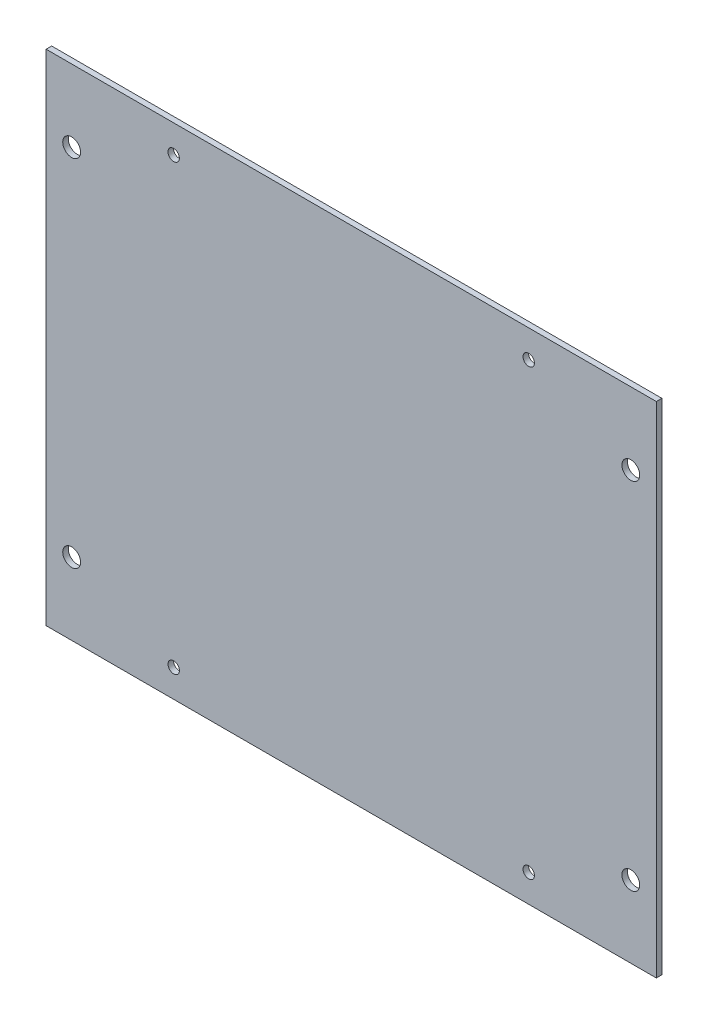
SolidWorks part; units mm, degrees
material "Perspex (TM) GS Acrylic Cast Sheet"
ref_plane "Front Plane" through (0, 0, 0) normal (0, 0, 1) x (1, 0, 0)
ref_plane "Top Plane" through (0, 0, 0) normal (0, 1, 0) x (1, 0, 0)
ref_plane "Right Plane" through (0, 0, 0) normal (1, 0, 0) x (0, 0, -1)
sketch "Sketch1" plane through (0, 0, 0) normal (0, 0, 1) x (1, 0, 0)
  line L1 (-457.2, -304.8) -> (457.2, -304.8)
  line L2 (-457.2, -304.8) -> (-457.2, 304.8)
  line L3 (-457.2, 304.8) -> (457.2, 304.8)
  line L4 (457.2, -304.8) -> (457.2, 304.8)
  line L5 (0, 304.8) -> (0, -304.8) construction
  line L6 (-457.2, 0) -> (457.2, 0) construction
  point P0 (0, 0)
  point P4 (-320.04, 0)
  point P5 (320.04, 0)
  point P6 (0, 213.36)
  point P7 (0, -213.36)
  dimension "Length" = 914.4
  dimension "Width" = 609.6
  dimension "Break" = 137.16
  dimension "D2" = 137.16
  dimension "D1" = 91.44
  dimension "D3" = 91.44
sketch "Sketch2" plane through (0, 0, 0) normal (1, 0, 0) x (0, 0, -1)
  line L0 (-0.7938, -304.8) -> (0.7938, -304.8)
  dimension "Thickness" = 1.5875
sketch "Sketch3" plane through (0, 0, 0) normal (0, 0, 1) x (1, 0, 0)
  line L0 (-457.2, -304.8) -> (-457.2, 304.8) construction
  line L1 (-457.2, -304.8) -> (457.2, -304.8) construction
  line L2 (457.2, -304.8) -> (457.2, 304.8) construction
  line L3 (-457.2, 304.8) -> (457.2, 304.8) construction
  line L4 (-457.2, -304.8) -> (-457.2, 304.8)
  line L5 (-457.2, -304.8) -> (457.2, -304.8)
  line L6 (457.2, -304.8) -> (457.2, 304.8)
  line L7 (-457.2, 304.8) -> (457.2, 304.8)
extrude "Boss-Extrude1" add sketch "Sketch3" along normal mid plane 1.5875
sketch "Sketch4" plane through (0, 0, -0.7937) normal (0, 0, -1) x (-1, 0, 0)
  line L0 (393.5597, -82.9526) -> (218.9347, -82.9526)
  line L1 (218.9347, -82.9526) -> (218.9347, 59.9224)
  line L2 (218.9347, 59.9224) -> (393.5597, 59.9224)
  line L3 (393.5597, 59.9224) -> (393.5597, -82.9526)
extrude "Cut-Extrude1" cut sketch "Sketch4" against normal blind 2.54 flip side to cut
hole_wizard "#4 Clearance Hole1" positions "Sketch9" profile "Sketch10" hole size "#4" standard "ANSI Inch" end condition through all
sketch "Sketch9" plane through (0, 0, -0.7937) normal (0, 0, -1) x (-1, 0, 0)
  line L0 (356.7455, 51.9595) -> (357.3855, 51.9595) construction
  point P0 (255.4472, -75.0151)
  point P6 (357.0655, 51.9595)
  point P16 (357.0472, -75.0151)
  point P28 (255.4472, 51.9849)
sketch "Sketch10" plane through (-255.4472, -75.0151, -0.7937) normal (1, 0, 0) x (0, 1, 0)
  line L0 (0, 0) -> (0, 1.5875)
  line L1 (0, 1.5875) -> (1.6319, 1.5875)
  line L2 (1.6319, 1.5875) -> (1.6319, 0)
  line L5 (1.6319, 0) -> (0, 0)
  line L11 (0, -6.35) -> (0, 107.95) construction
  dimension "Thru Hole Dia." = 3.2639
  dimension "Thru Hole Depth" = 1.5875
hole_wizard "#10 Clearance Hole1" positions "Sketch11" profile "Sketch12" hole size "#10" standard "ANSI Inch" end condition through all
sketch "Sketch11" plane through (0, 0, -0.7937) normal (0, 0, -1) x (-1, 0, 0)
  point P0 (226.2372, -62.3151)
  point P3 (226.2372, 39.2846)
  point P6 (386.2572, 39.2849)
  point P9 (386.2572, -62.3148)
sketch "Sketch12" plane through (-226.2372, -62.3151, -0.7937) normal (1, 0, 0) x (0, 1, 0)
  line L0 (0, 0) -> (0, 1.5875)
  line L1 (0, 1.5875) -> (2.5527, 1.5875)
  line L2 (2.5527, 1.5875) -> (2.5527, 0)
  line L5 (2.5527, 0) -> (0, 0)
  line L11 (0, -6.35) -> (0, 107.95) construction
  dimension "Thru Hole Dia." = 5.1054
  dimension "Thru Hole Depth" = 1.5875
equation "\"D1@Boss-Extrude1\"=\"thickness@sketch2\""
equation "\"Break@Sketch1\" = \"Length@Sketch1\" * 0.15"
equation "\"D2@Sketch1\" = \"Break@Sketch1\""
equation "\"D1@Sketch1\"=\"Width@Sketch1\"*0.15"
equation "\"D3@Sketch1\"=\"D1@Sketch1\""
